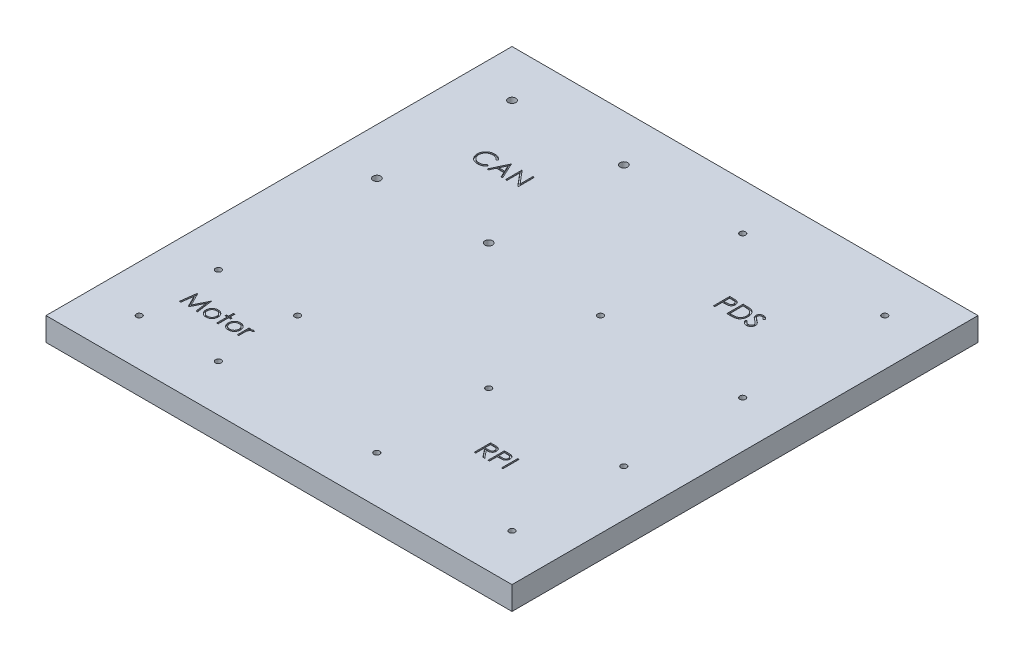
SolidWorks part; units mm, degrees
ref_plane "Front Plane" through (0, 0, 0) normal (0, 0, 1) x (1, 0, 0)
ref_plane "Top Plane" through (0, 0, 0) normal (0, 1, 0) x (1, 0, 0)
ref_plane "Right Plane" through (0, 0, 0) normal (1, 0, 0) x (0, 0, -1)
sketch "Sketch1" plane through (0, 0, 0) normal (0, 1, 0) x (1, 0, 0)
  line L1 (0, 0) -> (200, 0)
  line L2 (0, 0) -> (0, 200)
  line L3 (0, 200) -> (200, 200)
  line L4 (200, 0) -> (200, 200)
  circle A0 centre (180, 180) radius 1.25
  circle A1 centre (119, 180) radius 1.25
  circle A2 centre (100, 0) radius 1.25
  circle A3 centre (119, 119) radius 1.25
  circle A4 centre (100, 0) radius 1.25
  circle A5 centre (100, 0) radius 1.25
  circle A6 centre (180, 119) radius 1.25
  circle A7 centre (20, 180) radius 1.65
  circle A8 centre (68, 180) radius 1.65
  circle A9 centre (20, 122) radius 1.65
  circle A10 centre (68, 122) radius 1.65
  circle A11 centre (20, 20) radius 1.25
  circle A12 centre (20, 54) radius 1.25
  circle A13 centre (54, 54) radius 1.25
  circle A14 centre (54, 20) radius 1.25
  circle A15 centre (180, 68) radius 1.25
  circle A16 centre (180, 20) radius 1.25
  circle A17 centre (122, 68) radius 1.25
  circle A18 centre (122, 20) radius 1.25
  point P43 (0, 0)
  dimension "D3" = 2.5
  dimension "D6" = 61
  dimension "D10" = 2.5
  dimension "D19" = 3.3
  dimension "D20" = 3.3
  dimension "D21" = 3.3
  dimension "D22" = 3.3
  dimension "D23" = 2.5
  dimension "D26" = 2.5
  dimension "D27" = 2.5
  dimension "D28" = 2.5
  dimension "D38" = 2.5
  dimension "D39" = 2.5
  dimension "D43" = 2.5
  dimension "D44" = 2.5
  dimension "D1" = 200
  dimension "D2" = 200
  dimension "D4" = 20
  dimension "D5" = 20
  dimension "D7" = 20
  dimension "D8" = 61
  dimension "D9" = 0
  dimension "D11" = 20
  dimension "D12" = 20
  dimension "D13" = 58
  dimension "D14" = 0
  dimension "D15" = 20
  dimension "D16" = 48
  dimension "D17" = 0
  dimension "D18" = 0
  dimension "D24" = 20
  dimension "D25" = 20
  dimension "D29" = 0
  dimension "D30" = 34
  dimension "D31" = 34
  dimension "D32" = 0
  dimension "D33" = 34
  dimension "D34" = 20
  dimension "D35" = 0
  dimension "D36" = 48
  dimension "D37" = 20
  dimension "D40" = 58
  dimension "D41" = 0
  dimension "D42" = 58
extrude "Boss-Extrude2" add sketch "Sketch1" along normal blind 10 contours L1 L4 L3 L2
extrude "Cut-Extrude1" cut sketch "Sketch1<4>" along normal through all contours A11 | A14 | A13 | A12 | A9 | A10 | A8 | A7 | A3 | A6 | A0 | A1 | A16 | A15 | A17 | A18
sketch "Sketch1<4>" plane through (0, 0, 0) normal (0, 1, 0) x (1, 0, 0) same geometry as "Sketch1"
sketch "Sketch2" plane through (0, 10, 0) normal (0, 1, 0) x (1, 0, 0)
  circle A0 centre (20, 180) radius 1.65 construction
  circle A1 centre (68, 180) radius 1.65 construction
  circle A2 centre (68, 122) radius 1.65 construction
  circle A3 centre (122, 68) radius 1.25 construction
  circle A4 centre (180, 68) radius 1.25 construction
  circle A5 centre (122, 20) radius 1.25 construction
  text T0 "Motor" font "Century Gothic" height 7
  text T1 "RPI\r\n" font "Century Gothic" height 7
  text T2 "CAN" font "Century Gothic" height 7
  text T3 "PDS" font "Century Gothic" height 7
  point P4 (30.2107, 160.4377)
  dimension "D1" = 48
  dimension "D2" = 58
  dimension "D3" = 58
  dimension "D4" = 48
extrude "Cut-Extrude2" cut sketch "Sketch2" against normal blind 0.5
